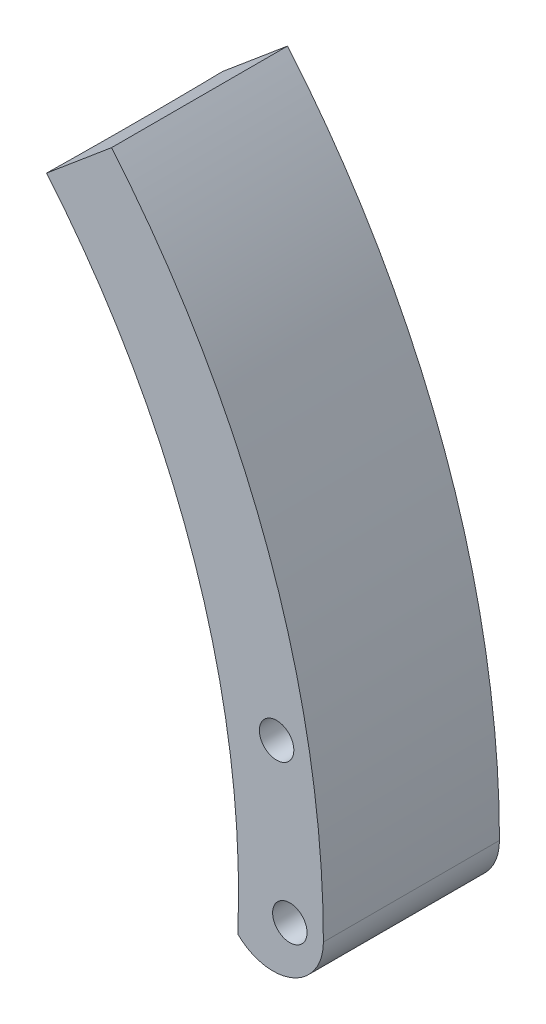
SolidWorks part; units mm, degrees
material "ABS"
ref_plane "Front Plane" through (0, 0, 0) normal (0, 0, 1) x (1, 0, 0)
ref_plane "Top Plane" through (0, 0, 0) normal (0, 1, 0) x (1, 0, 0)
ref_plane "Right Plane" through (0, 0, 0) normal (1, 0, 0) x (0, 0, -1)
sketch "Sketch2" plane through (0, 0, 0) normal (0, 0, 1) x (1, 0, 0)
  line L0 (0, 0) -> (152.4, 0) construction
  line L4 (152.4, 0) -> (171.45, 0) construction
  line L5 (0, 0) -> (212.62, 37.4906) construction
  line L6 (0, 0) -> (116.7452, 97.9608) construction
  line L7 (116.7452, 97.9608) -> (131.3383, 110.2059) construction
  line L8 (116.7452, 97.9608) -> (131.3383, 110.2059)
  circle A0 centre (165.1, 0) radius 3.2639
  circle A2 centre (162.5918, 28.6693) radius 3.2639
  arc A4 (152.4, 0) -> (116.7452, 97.9608) centre (0, 0) ccw
  arc A5 (171.45, 0) -> (131.3383, 110.2059) centre (0, 0) ccw
  arc A7 (152.4, 0) -> (171.45, 0) centre (161.925, 0) ccw
  point P16 (150.0847, 26.464)
  dimension "D5" = 6.5278
  dimension "D10" = 6.5278
  dimension "D1" = 152.4
  dimension "D2" = 19.05
  dimension "D4" = 12.7
  dimension "D8" = 215.9
  dimension "D9" = 10
  dimension "D12" = 40
  dimension "D13" = 12.7
extrude "Boss-Extrude1" add sketch "Sketch2" along normal blind 16.6687 and the other way blind 16.6687
sketch "Sketch3" plane through (0, 0, 0) normal (0, 1, 0) x (1, 0, 0)
  line L0 (0, 0) -> (31.75, 0) construction
  line L4 (152.4, 0) -> (152.4, -31.75) construction
  line L5 (31.75, 0) -> (31.75, 124.7577)
  line L6 (31.75, 0) -> (31.75, -124.7577)
  line L7 (0, -1000) -> (0, 49000) construction
  arc A0 (31.75, -124.7577) -> (31.75, 124.7577) centre (31.75, 0) ccw
  dimension "D1" = 31.75
  dimension "D2" = 31.75
  dimension "D3" = 152.4
revolve "Cut-Revolve2" cut sketch "Sketch3" angle 360 about L7
